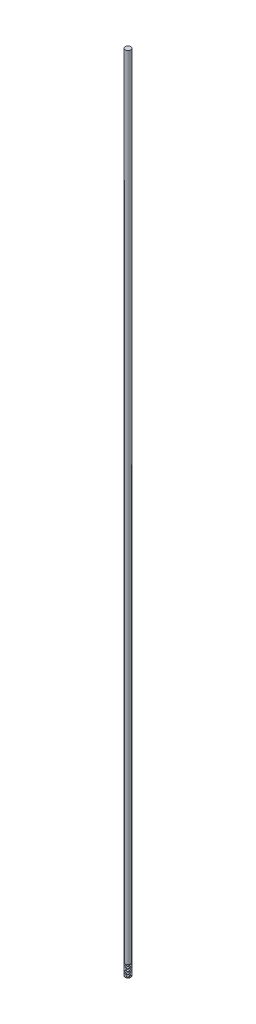
SolidWorks part; units mm, degrees
ref_plane "Front Plane" through (0, 0, 0) normal (0, 0, 1) x (1, 0, 0)
ref_plane "Top Plane" through (0, 0, 0) normal (0, 1, 0) x (1, 0, 0)
ref_plane "Right Plane" through (0, 0, 0) normal (1, 0, 0) x (0, 0, -1)
sketch "Sketch1" plane through (0, 0, 0) normal (0, 1, 0) x (1, 0, 0)
  circle A0 centre (0, 0) radius 2.413
  dimension "D1" = 4.826
extrude "Boss-Extrude1" add sketch "Sketch1" along normal blind 696.976
thread "Thread1" pitch 0.3175 method cut profile "Thread Profile1" start angle 0, offset 0, length 9.906, pitch 0.3175, diameter 4.826
ref_plane "Plane1" through (2.413, 0, 0) normal (0, 0, 1) x (1, 0, 0)
sketch "Thread Profile1" plane through (2.413, 0, 0) normal (0, 0, 1) x (1, 0, 0)
  line L0 (0, 0) -> (0, 0.3175) construction
  line L11 (0, 0) -> (0, 0.2778)
  line L12 (0, 0.2778) -> (-0.1719, 0.1786)
  line L13 (-0.1719, 0.1786) -> (-0.1719, 0.0992)
  line L15 (-0.1719, 0.0992) -> (0, 0)
  line L17 (-0.1719, 0.1389) -> (0, 0.1389) construction
  point P2 (0, 0)
  dimension "Pitch" = 0.3175
  dimension "Profile_Angle" = 60
  dimension "Profile_Land" = 0.0794
  dimension "Profile_Height" = 0.1719
